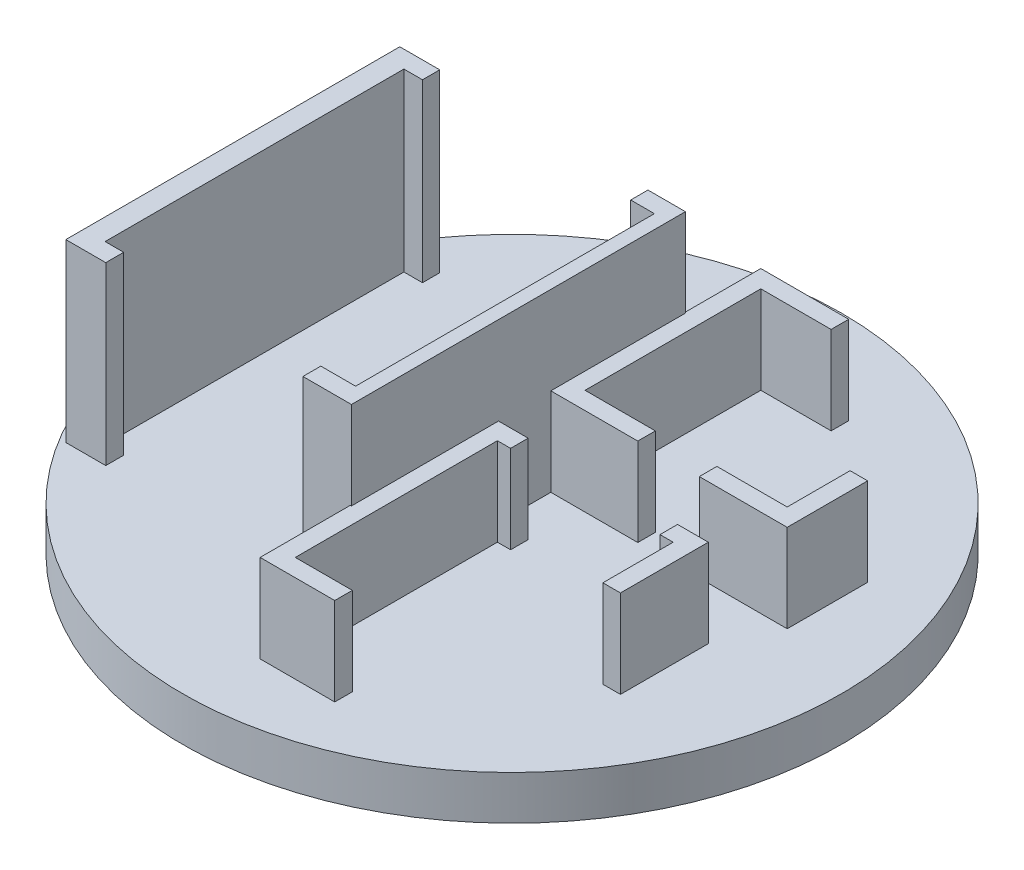
SolidWorks part; units mm, degrees
ref_plane "Ebene vorne" through (0, 0, 0) normal (0, 0, 1) x (1, 0, 0)
ref_plane "Ebene oben" through (0, 0, 0) normal (0, 1, 0) x (1, 0, 0)
ref_plane "Ebene rechts" through (0, 0, 0) normal (1, 0, 0) x (0, 0, -1)
sketch "Skizze1" plane through (0, 0, 0) normal (0, 1, 0) x (1, 0, 0)
  line L0 (0, 0) -> (0, -75)
  line L1 (0, -37.5) -> (-48.465, -37.5) construction
  arc A1 (0, -75) -> (0, 0) centre (0, -37.5) cw
  dimension "D1" = 75
extrude "Aufsatz-Linear austragen1" add sketch "Skizze1" along normal blind 5
sketch "Skizze15" plane through (0, 5, 0) normal (0, 1, 0) x (1, 0, 0)
  line L0 (-5.4494, -26.8176) -> (-14.4494, -26.8176) construction
  line L2 (3.0051, -32.2011) -> (3.0051, -30.7011)
  line L3 (3.0051, -32.2011) -> (11.0051, -32.2011)
  line L4 (26.0051, -32.2011) -> (26.0051, -30.7011)
  line L5 (3.0051, -12.2011) -> (11.0051, -12.2011)
  line L6 (1.0051, -34.2011) -> (1.0051, -30.7011)
  line L8 (28.0051, -34.2011) -> (28.0051, -30.7011)
  line L9 (1.0051, -10.2011) -> (11.0051, -10.2011)
  line L10 (11.0051, -32.2011) -> (11.0051, -34.2011)
  line L11 (18.0051, -32.2011) -> (18.0051, -34.2011)
  line L13 (18.0051, -32.2011) -> (26.0051, -32.2011)
  line L15 (11.0051, -12.2011) -> (11.0051, -10.2011)
  line L23 (1.0051, -13.7011) -> (1.0051, -10.2011)
  line L24 (3.0051, -13.7011) -> (3.0051, -12.2011)
  line L28 (3.0051, -34.2011) -> (11.0051, -34.2011)
  line L32 (26.0051, -34.2011) -> (18.0051, -34.2011)
  line L33 (28.0051, -34.2011) -> (26.0051, -34.2011)
  line L34 (3.0051, -34.2011) -> (1.0051, -34.2011)
  line L35 (28.0051, -30.7011) -> (28.0051, -25.0424)
  line L36 (28.0051, -25.0424) -> (26.0051, -25.0424)
  line L37 (26.0051, -25.0424) -> (26.0051, -30.7011)
  line L38 (3.0051, -30.7011) -> (3.0051, -13.7011)
  line L39 (1.0051, -13.7011) -> (1.0051, -30.7011)
sketch "Skizze19" plane through (0, 5, 0) normal (0, 1, 0) x (1, 0, 0)
  line L0 (0, -37.5) -> (-52.774, -37.5) construction
  line L1 (0, -75) -> (0, 0) construction
  line L2 (-28.9568, -75) -> (-28.9568, 0) construction
  line L3 (-0.4568, -20.8495) -> (-0.4568, -54.8495)
  line L4 (-0.4568, -20.8495) -> (-28.9568, -20.8495)
  line L5 (-28.9568, -20.8495) -> (-28.9568, -54.8495)
  line L6 (-28.9568, -54.8495) -> (-0.4568, -54.8495)
  line L7 (-31.3875, -18.8876) -> (1.1125, -18.8876)
  line L8 (-31.3875, -18.8876) -> (-31.3875, -56.8876)
  line L9 (-31.3875, -56.8876) -> (1.1125, -56.8876)
  line L10 (1.1125, -56.8876) -> (1.1125, -18.8876)
extrude "Aufsatz-Linear austragen2" add sketch "Skizze19" along normal blind 20
sketch "Skizze20" plane through (0, 5, 0) normal (0, 1, 0) x (1, 0, 0)
  line L0 (0, -75) -> (0, 0)
  arc A0 (0, 0) -> (0, -75) centre (0, -37.5) cw
extrude "Aufsatz-Linear austragen3" add sketch "Skizze20" against normal blind 5
extrude "Aufsatz-Linear austragen5" add sketch "Skizze15" along normal blind 10
sketch "Skizze22" plane through (0, 25, 0) normal (0, 1, 0) x (1, 0, 0)
  line L0 (-4.4095, -54.8495) -> (-26.8437, -54.8495)
  line L1 (-28.9568, -54.8495) -> (-0.4568, -54.8495) construction
  line L2 (-26.8437, -54.8495) -> (-26.8437, -56.8876)
  line L3 (-31.3875, -56.8876) -> (1.1125, -56.8876) construction
  line L4 (-26.8437, -56.8876) -> (-4.4095, -56.8876)
  line L5 (-4.4095, -56.8876) -> (-4.4095, -54.8495)
  line L12 (-3.1509, -20.8495) -> (-26.8437, -20.8495)
  line L13 (-0.4568, -20.8495) -> (-28.9568, -20.8495) construction
  line L14 (-26.8437, -20.8495) -> (-26.8437, -18.8876)
  line L15 (1.1125, -18.8876) -> (-31.3875, -18.8876) construction
  line L16 (-26.8437, -18.8876) -> (-3.1509, -18.8876)
  line L17 (-3.1509, -18.8876) -> (-3.1509, -20.8495)
extrude "Schnitt-Linear austragen1" cut sketch "Skizze22" against normal blind 20
sketch "Skizze25" plane through (0, 5, 0) normal (0, 1, 0) x (1, 0, 0)
  line L0 (-6.7585, -58.6134) -> (-15.7585, -58.6134) construction
  line L4 (22.9867, -42.1547) -> (21.4867, -42.1547)
  line L5 (2.9867, -65.1547) -> (2.9867, -57.1547)
  line L7 (24.9867, -40.1547) -> (21.4867, -40.1547)
  line L8 (0.9867, -67.1547) -> (0.9867, -57.1547)
  line L10 (22.9867, -50.1547) -> (24.9867, -50.1547)
  line L11 (22.9867, -50.1547) -> (22.9867, -42.1547)
  line L15 (4.4867, -42.1547) -> (4.4867, -40.1547)
  line L16 (21.4867, -42.1547) -> (21.4867, -40.1547)
  line L17 (2.9867, -50.1547) -> (2.9867, -42.1547)
  line L18 (0.9867, -50.1547) -> (0.9867, -40.1547)
  line L19 (4.4867, -40.1547) -> (0.9867, -40.1547)
  line L20 (4.4867, -42.1547) -> (2.9867, -42.1547)
  line L21 (4.4867, -67.1547) -> (0.9867, -67.1547)
  line L22 (4.4867, -65.1547) -> (2.9867, -65.1547)
  line L24 (24.9867, -42.1547) -> (24.9867, -50.1547)
  line L25 (24.9867, -40.1547) -> (24.9867, -42.1547)
  line L27 (4.4867, -65.1547) -> (9.478, -65.1547)
  line L28 (9.478, -65.1547) -> (9.478, -67.1547)
  line L29 (9.478, -67.1547) -> (4.4867, -67.1547)
  line L30 (2.9867, -57.1547) -> (2.9867, -50.1547)
  line L31 (0.9867, -57.1547) -> (0.9867, -50.1547)
extrude "Aufsatz-Linear austragen6" add sketch "Skizze25" along normal blind 10
